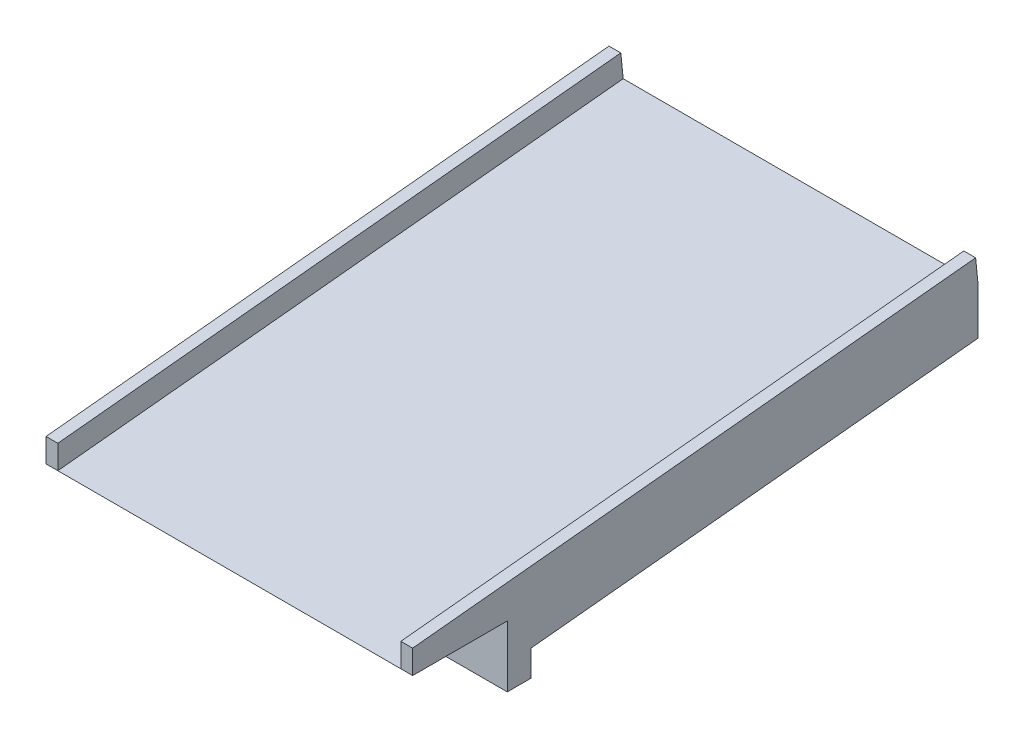
SolidWorks part; units mm, degrees
ref_plane "Front Plane" through (0, 0, 0) normal (0, 0, 1) x (1, 0, 0)
ref_plane "Top Plane" through (0, 0, 0) normal (0, 1, 0) x (1, 0, 0)
ref_plane "Right Plane" through (0, 0, 0) normal (1, 0, 0) x (0, 0, -1)
sketch "Sketch4" plane through (0, 0, 0) normal (1, 0, 0) x (0, 0, -1)
  line L0 (0, 0) -> (0, 20)
  line L1 (0, 0) -> (198.9975, 20)
  line L2 (0, 20) -> (198.9975, 40)
  line L3 (198.9975, 20) -> (198.9975, 40)
  line L4 (0, 55) -> (0, -55) construction
  line L5 (0, 20) -> (-40, 15.9798)
  line L6 (-40, 15.9798) -> (0, 15.9798)
  point P10 (0, 0)
  point P11 (-1.5825, 20)
  dimension "D1" = 20
  dimension "D2" = 200
  dimension "D3" = 20
  dimension "D4" = 40
extrude "Boss-Extrude1" add sketch "Sketch4" along normal blind 155 contours L1 L3 L2 L0 | L5 L6 L0 region at (0, 20, -99.4987) region at (0, 17.3199, 13.3333)
sketch "Sketch7" plane through (0, 0, 0) normal (0, 0, 1) x (1, 0, 0)
  line L1 (0, 10) -> (155, 10)
  line L2 (0, 10) -> (0, -10)
  line L3 (0, -10) -> (155, -10)
  line L4 (155, 10) -> (155, -10)
  line L5 (0, 20) -> (0, 10) construction
  line L8 (155, 0) -> (155, 15.9798) construction
  point P4 (0, 6.8938)
  point P5 (0, 0)
  point P9 (0, 0)
  dimension "D1" = 20
  dimension "D2" = 10
  dimension "D3" = 155
extrude "Boss-Extrude4" add sketch "Sketch7" against normal blind 10
sketch "Sketch8" plane through (0, 19.8, 1.99) normal (0, 0.995, 0.1) x (1, 0, 0)
  line L0 (155, -38.2015) -> (0, -38.2015) construction
  line L1 (0, 202) -> (5, 202)
  line L2 (0, 202) -> (0, -38.2015)
  line L3 (0, -38.2015) -> (5, -38.2015)
  line L4 (5, 202) -> (5, -38.2015)
  line L6 (155, 202) -> (150, 202)
  line L7 (155, 202) -> (155, -38.2015)
  line L8 (155, -38.2015) -> (150, -38.2015)
  line L9 (150, 202) -> (150, -38.2015)
  dimension "D1" = 5
  dimension "D2" = 5
extrude "Boss-Extrude5" add sketch "Sketch8" along normal blind 10
sketch "Sketch9" plane through (155, 0, 0) normal (1, 0, 0) x (0, 0, -1)
  line L0 (-40, 15.9798) -> (-40, 26.0302)
  line L1 (-41, 25.9297) -> (197.9975, 49.9499) construction
  line L2 (-40, 26.0302) -> (-41, 25.9297)
  line L3 (-41, 25.9297) -> (-40, 15.9798)
extrude "Cut-Extrude1" cut sketch "Sketch9" against normal through all
